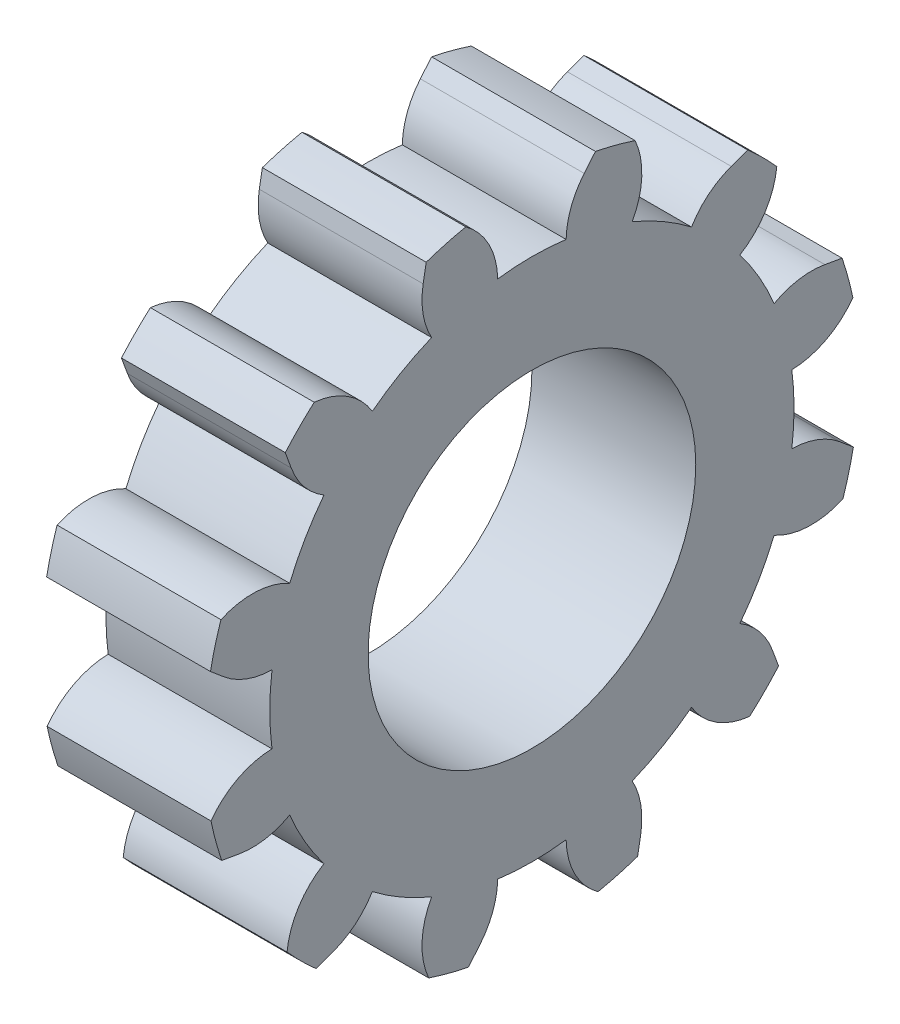
SolidWorks part; units mm, degrees
ref_plane "Front Plane" through (0, 0, 0) normal (0, 0, 1) x (1, 0, 0)
ref_plane "Top Plane" through (0, 0, 0) normal (0, 1, 0) x (1, 0, 0)
ref_plane "Right Plane" through (0, 0, 0) normal (1, 0, 0) x (0, 0, -1)
sketch "Sketch3" plane through (0, 0, 0) normal (1, 0, 0) x (0, 0, -1)
  circle A0 centre (0, 0) radius 10
  circle A1 centre (0, 0) radius 5
  circle A2 centre (0, 0) radius 9
  circle A3 centre (0, 0) radius 8
  dimension "D1" = 20
  dimension "D2" = 18
  dimension "D3" = 10
  dimension "D4" = 16
extrude "Boss-Extrude1" add sketch "Sketch3" along normal blind 5 contours A1 | A3 A1 | A2 A3 | A0 A2 region at (0, 0, 9.7172) region at (0, 0, 0) region at (0, 0, 8.7454) region at (0, 0, 7.7737)
sketch "Gear_Profile" plane through (0, 0, 0) normal (-1, 0, 0) x (0, 0, 1)
  line L0 (0, 0) -> (0, 13.9827) construction
  line L1 (0, 7.5) -> (-2.6395, 10.6456)
  line L2 (-2.7176, 10.1422) -> (0, 0)
  line L3 (0, 0) -> (2.7176, 10.1422)
  line L4 (-1.0442, 7.9316) -> (0, 0)
  line L5 (1.0442, 7.9316) -> (0, 0)
  arc A0 (-1.0442, 7.9316) -> (1.0442, 7.9316) centre (0, 0) cw
  circle A1 centre (0, 0) radius 8 construction
  arc A2 (-2.7176, 10.1422) -> (2.7176, 10.1422) centre (0, 0) cw
  circle A3 centre (0, 0) radius 10 construction
  arc A4 (-2.7176, 10.1422) -> (-1.0442, 7.9316) centre (-3.4017, 7.8857) cw
  arc A5 (2.7176, 10.1422) -> (1.0442, 7.9316) centre (3.4017, 7.8857) ccw
  circle M7 centre (0, 0) radius 10
  dimension "D1" = 0.5
  dimension "D2" = 7.5
  dimension "D3" = 40
  dimension "D4" = 30
  dimension "D5" = 15
extrude "Cut-Extrude1" cut sketch "Gear_Profile" against normal blind 5 contours A0 L0 L1 M7 | L1 A4 A0 | L0 A0 A5 M7 region at (0, 8.3419, -0.9131) region at (0, 9.0788, 0.7112) region at (0, 9.18, -0.6767)
pattern_circular "CirPattern1" count 12 over 360 about axis through (5, 0, 0) along (-1, 0, 0) of "Cut-Extrude1" reverse direction yes
extrude "Cut-Extrude3" cut sketch "Sketch3<3>" along normal blind 5 contours A1 region at (0, 0, 0)
sketch "Sketch3<3>" plane through (0, 0, 0) normal (1, 0, 0) x (0, 0, -1) same geometry as "Sketch3"
